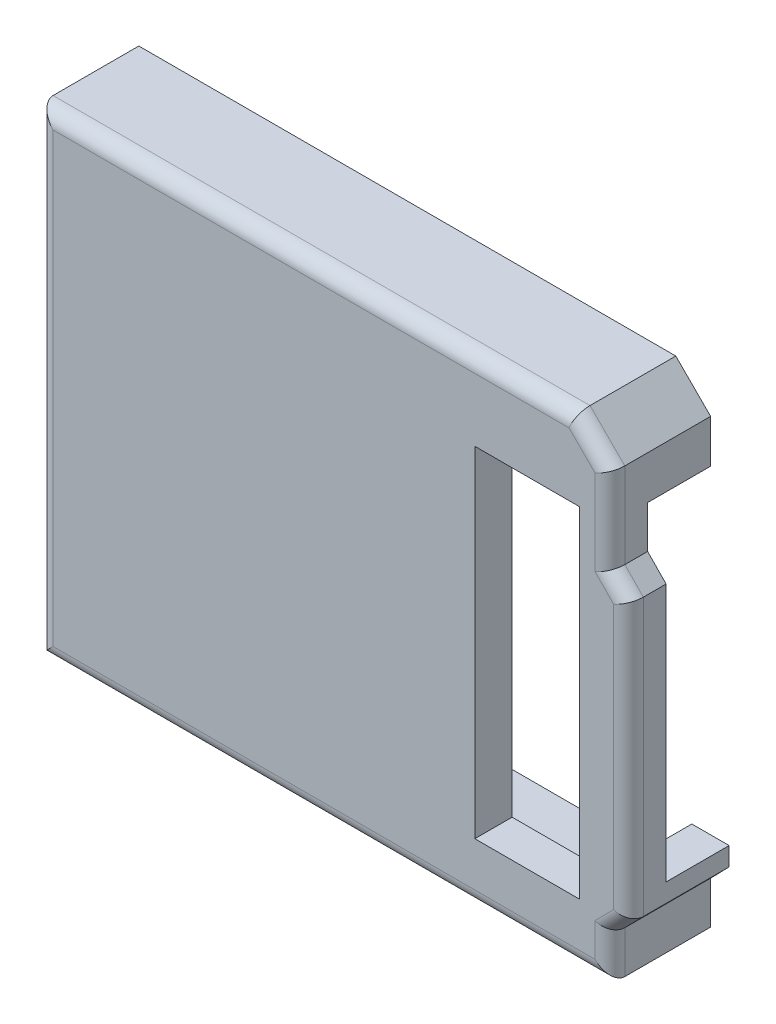
SolidWorks part; units mm, degrees
ref_plane "Front Plane" through (0, 0, 0) normal (0, 0, 1) x (1, 0, 0)
ref_plane "Top Plane" through (0, 0, 0) normal (0, 1, 0) x (1, 0, 0)
ref_plane "Right Plane" through (0, 0, 0) normal (1, 0, 0) x (0, 0, -1)
sketch "Sketch4" plane through (0, 0, 0) normal (0, 0, 1) x (1, 0, 0)
  line L25 (-58.7815, 16.139) -> (-58.7815, -3.121)
  line L26 (-58.7815, -3.121) -> (-54.0815, -3.121)
  line L27 (-54.0815, -3.121) -> (-54.0815, 16.139)
  line L28 (-54.0815, 16.139) -> (-58.7815, 16.139)
  line L29 (-54.0815, -12.7107) -> (-58.7815, -12.7107)
  line L30 (-58.7815, -12.7107) -> (-58.7815, -20.8795)
  line L31 (-58.7815, -20.8795) -> (17.8885, -20.8795)
  line L32 (17.8885, -20.8795) -> (17.8885, -15.1978)
  line L33 (17.8885, -15.1978) -> (20.3685, -12.6578)
  line L34 (20.3685, -12.6578) -> (20.3685, 24.4249)
  line L35 (20.3685, 24.4249) -> (17.8885, 26.9649)
  line L36 (17.8885, 26.9649) -> (17.8885, 38.4295)
  line L37 (17.8885, 38.4295) -> (13.2191, 43.099)
  line L38 (13.2191, 43.099) -> (-58.7815, 43.099)
  line L39 (-58.7815, 43.099) -> (-58.7815, 28.739)
  line L40 (-58.7815, 28.739) -> (-54.0815, 28.739)
  line L41 (-54.0815, 28.739) -> (-54.0815, 38.399)
  line L42 (-54.0815, 38.399) -> (13.1885, 38.399)
  line L43 (13.1885, 38.399) -> (13.1885, 25.0509)
  line L44 (13.1885, 25.0509) -> (15.6685, 22.5109)
  line L45 (15.6685, 22.5109) -> (15.6685, -10.7438)
  line L46 (15.6685, -10.7438) -> (13.1885, -13.2838)
  line L47 (13.1885, -13.2838) -> (13.1885, -16.1795)
  line L48 (13.1885, -16.1795) -> (-54.0815, -16.1795)
  line L49 (-54.0815, -16.1795) -> (-54.0815, -12.7107)
  line L51 (-58.7815, 28.739) -> (-54.0815, 28.739)
  line L52 (-58.7815, 28.739) -> (-58.7815, 16.139)
  line L53 (-58.7815, 16.139) -> (-54.0815, 16.139)
  line L54 (-54.0815, 28.739) -> (-54.0815, 16.139)
  line L55 (-58.7815, -3.121) -> (-54.0815, -3.121)
  line L56 (-58.7815, -3.121) -> (-58.7815, -12.7107)
  line L57 (-58.7815, -12.7107) -> (-54.0815, -12.7107)
  line L58 (-54.0815, -3.121) -> (-54.0815, -12.7107)
extrude "Boss-Extrude1" add sketch "Sketch4" along normal blind 13.5 contours L27 L58 L49 L48 L47 L46 L45 L44 L43 L42 L41 L54 | L48 L49 L29 L30 L31 L32 L33 L34 L35 L36 L37 L38 L39 L40 L41 L42 L43 L44 L45 L46 L47 | L54 L40 L52 L28 | L27 L28 L25 L26 | L58 L26 L56 L29 region at (-56.4315, 6.509, 0) region at (-56.4315, 22.439, 0) region at (-56.4315, -7.9158, 0) region at (-19.6238, 10.9864, 0) region at (-57.7637, 35.919, 0)
sketch "Sketch6" plane through (0, 0, 0) normal (0, 0, -1) x (-1, 0, 0)
  line L54 (53.7815, -15.8795) -> (53.7815, 38.099)
  line L55 (-12.8885, -15.8795) -> (53.7815, -15.8795)
  line L56 (-15.3685, -10.6216) -> (-12.8885, -13.1616)
  line L57 (-15.3685, 22.3887) -> (-15.3685, -10.6216)
  line L58 (-12.8885, 24.9287) -> (-15.3685, 22.3887)
  line L59 (-12.8885, 36.3585) -> (-12.8885, 24.9287)
  line L60 (53.7815, 38.099) -> (-11.148, 38.099)
  line L61 (53.7815, -15.8795) -> (53.7815, 38.099)
  line L62 (-12.8885, -15.8795) -> (53.7815, -15.8795)
  line L63 (-15.3685, -10.6216) -> (-12.8885, -13.1616)
  line L64 (-15.3685, 22.3887) -> (-15.3685, -10.6216)
  line L65 (-12.8885, 24.9287) -> (-15.3685, 22.3887)
  line L66 (-12.8885, 36.3585) -> (-12.8885, 24.9287)
  line L67 (53.7815, 38.099) -> (-11.148, 38.099)
  line L68 (-12.8885, -13.1616) -> (-12.8885, -15.8795)
  line L69 (-12.8885, -13.1616) -> (-12.8885, -15.8795)
  line L70 (-11.148, 38.099) -> (-12.8885, 36.3585)
  line L71 (-11.148, 38.099) -> (-12.8885, 36.3585)
  dimension "D1" = 5
extrude "Cut-Extrude1" cut sketch "Sketch6" against normal blind 8.5
fillet "Fillet2" radius 2 9 edges at (19.1285, 25.6949, 13.5) (17.8885, 32.6972, 13.5) (15.5538, 40.7643, 13.5) (-22.7812, 43.099, 13.5) (-58.7815, 11.1098, 13.5) (-20.4465, -20.8795, 13.5) (17.8885, -18.0386, 13.5) (19.1285, -13.9278, 13.5) (20.3685, 5.8835, 13.5)
sketch "Sketch8" plane through (20.3685, 0, 0) normal (1, 0, 0) x (0, 0, -1)
  line L5 (-11.5, -12.6578) -> (0, -12.6578) construction
  line L6 (-10.4467, -12.6578) -> (-10.4467, -10.1678)
  line L12 (-11.2867, 38.4295) -> (-11.2867, 34.5795)
  line L13 (-11.5, 38.4295) -> (0, 38.4295) construction
  line L14 (-11.2867, 34.5795) -> (-11.2867, 32.6395)
  line L19 (-10.4467, 31.3092) -> (-8.4467, 31.3092)
  line L25 (-8.4467, 32.6395) -> (0, 32.6395)
  line L26 (-8.4467, 32.6395) -> (-8.4467, -10.1678)
  line L27 (-8.4467, -10.1678) -> (0, -10.1678)
  line L28 (0, 32.6395) -> (0, -10.1678)
  line M5 (0, 24.4249) -> (-11.5, 24.4249)
  line M8 (0, -12.6578) -> (0, 24.4249)
  dimension "D1" = 2.49
  dimension "D2" = 3.85
  dimension "D3" = 1.94
  dimension "D4" = 2
extrude "Cut-Extrude2" cut sketch "Sketch8" against normal blind 40 and the other way blind 19 contours M5 | M8 M5 region at (20.3685, 28.5322, 4.2233) region at (20.3685, 7.1285, 4.2233)
sketch "Sketch9" plane through (0, 0, 13.5) normal (0, 0, 1) x (1, 0, 0)
  line L0 (4.7395, 34.9864) -> (4.7395, 32.6464)
  line L10 (-0.2281, 32.6464) -> (13.7773, 32.6464)
  line L11 (-0.2281, 32.6464) -> (-0.2281, -12.9252)
  line L12 (-0.2281, -12.9252) -> (13.7773, -12.9252)
  line L13 (13.7773, 32.6464) -> (13.7773, -12.9252)
  dimension "D1" = 2.34
extrude "Cut-Extrude3" cut sketch "Sketch9" against normal blind 25 contours L13 L10 L11 L12 region at (6.7746, 9.8606, 13.5)
